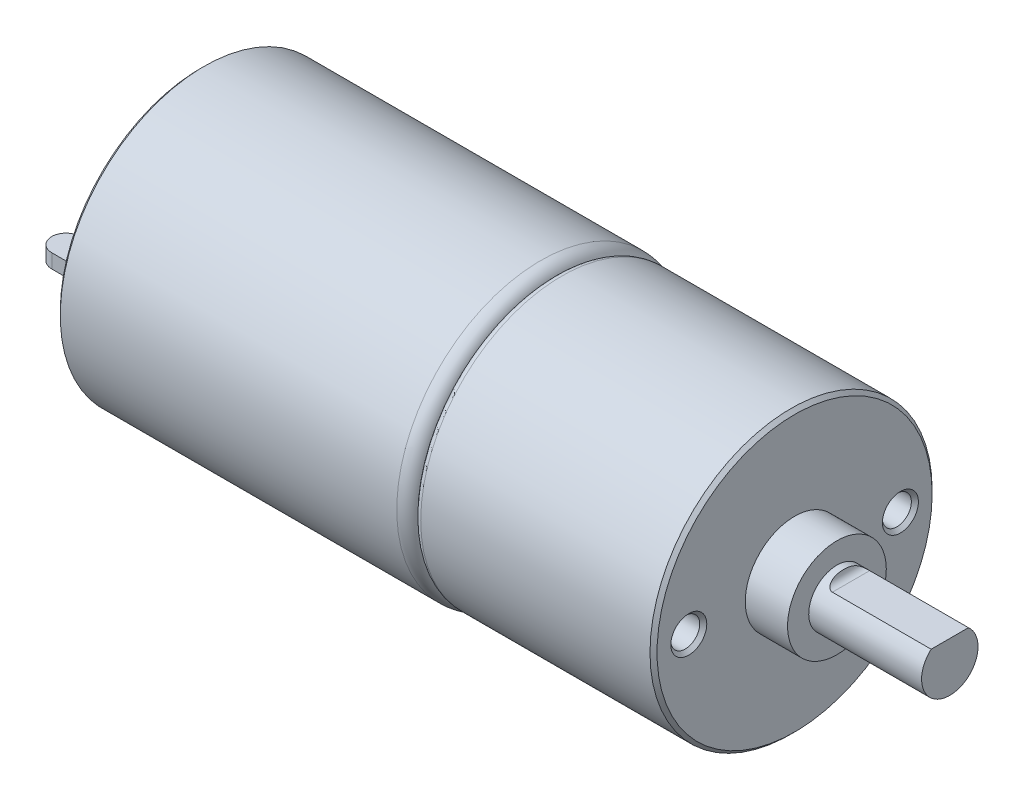
SolidWorks part; units mm, degrees
ref_plane "Front Plane" through (0, 0, 0) normal (0, 0, 1) x (1, 0, 0)
ref_plane "Top Plane" through (0, 0, 0) normal (0, 1, 0) x (1, 0, 0)
ref_plane "Right Plane" through (0, 0, 0) normal (1, 0, 0) x (0, 0, -1)
sketch "Sketch1" plane through (0, 0, 0) normal (1, 0, 0) x (0, 0, -1)
  circle A0 centre (0, 0) radius 10.2
  dimension "D1" = 20.4
extrude "Boss-Extrude1" add sketch "Sketch1" along normal blind 25.1
fillet "Fillet1" radius 1 1 edges at (25.1, 0, -10.2)
sketch "Sketch2" plane through (25.1, 0, 0) normal (1, 0, 0) x (0, 0, -1)
  circle A2 centre (0, 0) radius 10
  dimension "D1" = 20
extrude "Boss-Extrude2" add sketch "Sketch2" along normal blind 17
fillet "Fillet2" radius 0.5 1 edges at (25.1, 0, -10)
chamfer "Chamfer1" distance 0.25 angle 45 2 edges at (0, 0, -10.2) (42.1, 0, -10)
sketch "Sketch3" plane through (42.1, 0, 0) normal (1, 0, 0) x (0, 0, -1)
  circle A0 centre (0, 0) radius 3.5
  dimension "D1" = 7
extrude "Boss-Extrude3" add sketch "Sketch3" along normal blind 3
sketch "Sketch4" plane through (42.1, 0, 0) normal (1, 0, 0) x (0, 0, -1)
  circle A1 centre (0, 0) radius 2
  dimension "D1" = 4
extrude "Boss-Extrude4" add sketch "Sketch4" along normal blind 11
sketch "Sketch6" plane through (0, 0, 0) normal (0, 0, 1) x (1, 0, 0)
  line L2 (53.1, 2) -> (45.6, 2)
  line L3 (53.1, -2) -> (53.1, 2)
  line L4 (53.1, -2) -> (53.1, 2) construction
  line L5 (53.1, 2) -> (53.1, 1.5)
  line L6 (53.1, 1.5) -> (46.1, 1.5)
  arc A0 (45.6, 2) -> (46.1, 1.5) centre (46.1, 2) ccw
  dimension "D2" = 3.5
  dimension "D3" = 7
  dimension "D1" = 0
extrude "Cut-Extrude1" cut sketch "Sketch6" against normal through all both and the other way through all
hole_wizard "M2.5x0.45 Tapped Hole1" positions "Sketch7" profile "Sketch8" tap size "M2.5x0.45" standard "ANSI Metric"
sketch "Sketch7" plane through (42.1, 0, 0) normal (1, 0, 0) x (0, 0, -1)
  point P0 (-7.5, 0)
  point P2 (7.5, 0)
  dimension "D1" = 7.5
  dimension "D2" = 7.5
cosmetic thread "Hole Thread1" parameters "D1"=41.85, "D2"=2.5
cosmetic thread "Hole Thread2" parameters "D1"=41.85, "D2"=2.5
sketch "Sketch8" plane through (42.1, 0, 7.5) normal (0, 1, 0) x (0, 0, -1)
  line L0 (0, 0) -> (0, 5.6159)
  line L1 (0, 5.6159) -> (1.025, 5)
  line L2 (1.025, 5) -> (1.025, 0.25)
  line L3 (1.025, 0.25) -> (1.275, 0)
  line L5 (1.275, 0) -> (0, 0)
  line L6 (-1.025, 0.25) -> (-1.275, 0) construction
  line L10 (0, 5.6159) -> (-1.025, 5) construction
  line L11 (0, -6.35) -> (0, 107.95) construction
  dimension "Tap Drill Dia." = 2.05
  dimension "Tap Drill Depth" = 5
  dimension "Near C'Sink Dia." = 2.55
  dimension "Near C'Sink Angle" = 90
  dimension "Drill Angle" = 118
sketch "Sketch9" plane through (0, 0, 0) normal (-1, 0, 0) x (0, 0, 1)
  line L0 (-5.15, 0) -> (0, 0) construction
  line L9 (-7.15, 0.5) -> (-5.15, 0.5)
  line L10 (-7.15, 0.5) -> (-7.15, -0.5)
  line L11 (-7.15, -0.5) -> (-5.15, -0.5)
  line L12 (-5.15, 0.5) -> (-5.15, -0.5)
  line L13 (5.15, 0.5) -> (7.15, 0.5)
  line L14 (5.15, 0.5) -> (5.15, -0.5)
  line L15 (5.15, -0.5) -> (7.15, -0.5)
  line L16 (7.15, 0.5) -> (7.15, -0.5)
  line L17 (0, 0) -> (5.15, 0) construction
  dimension "D1" = 2
  dimension "D2" = 1
  dimension "D3" = 2
  dimension "D4" = 1
  dimension "D5" = 5.15
  dimension "D6" = 5.15
extrude "Boss-Extrude5" add sketch "Sketch9" along normal blind 4.4
fillet "Fillet3" radius 1 4 edges at (-4.4, 0, 7.15) (-4.4, 0, 5.15) (-4.4, 0, -5.15) (-4.4, 0, -7.15)
